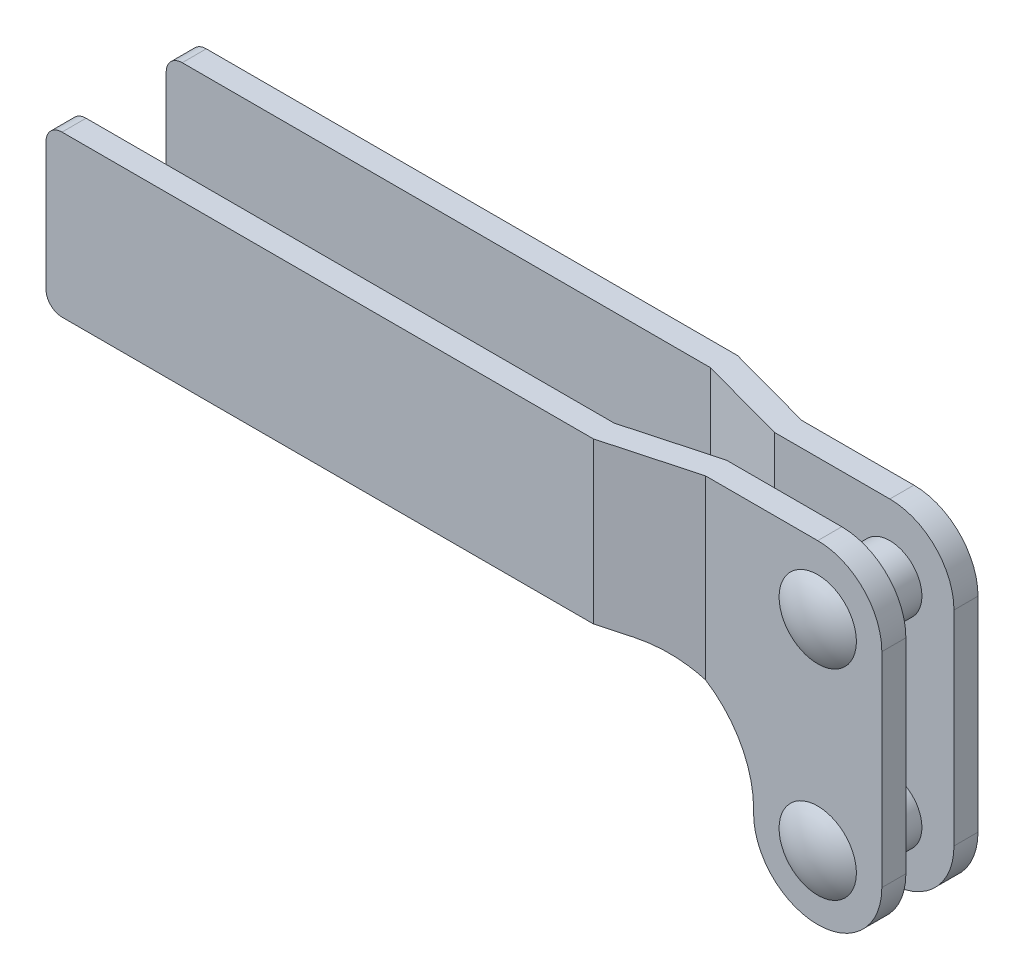
SolidWorks part; units mm, degrees
ref_plane "前视基准面" through (0, 0, 0) normal (0, 0, 1) x (1, 0, 0)
ref_plane "上视基准面" through (0, 0, 0) normal (0, 1, 0) x (1, 0, 0)
ref_plane "右视基准面" through (0, 0, 0) normal (1, 0, 0) x (0, 0, -1)
ref_plane "基准面1" through (0, 0, 0) normal (0, 1, 0) x (1, 0, 0)
ref_plane "基准面2" through (0, -8, 0) normal (0, 1, 0) x (1, 0, 0)
sketch "草图1" plane through (0, -8, 0) normal (0, 1, 0) x (1, 0, 0)
  line L0 (-93.3, -6) -> (-93.3, -9)
  line L1 (-93.3, -9) -> (-25, -9)
  line L2 (-25, -9) -> (-14, -6)
  line L3 (-14, -6) -> (8, -6)
  line L4 (8, -6) -> (8, -3)
  line L5 (8, -3) -> (-14.4018, -3)
  line L6 (-14.4018, -3) -> (-25.4018, -6)
  line L7 (-25.4018, -6) -> (-93.3, -6)
extrude "凸台-拉伸1" add sketch "草图1" along normal blind 41.5
ref_plane "基准面3" through (0, 0, 0) normal (1, 0, 0) x (0, 0, -1)
sketch "草图2" plane through (0, 0, 0) normal (1, 0, 0) x (0, 0, -1)
  line L0 (-6, 4.8218) -> (-6, 4)
  line L1 (-6, 4) -> (6, 4)
  line L2 (6, 4) -> (6, 4.5)
  line L3 (6, 4.5) -> (7, 4.5)
  line L4 (7, 4.5) -> (7, 0)
  line L5 (7, 0) -> (-7.5, 0)
  line L6 (7, 0) -> (-7.5, 0) construction
  arc A0 (-7.5, 0) -> (-6, 4.8218) centre (1, 0) cw
revolve "旋转1" add sketch "草图2" angle 360 about L6 reverse direction yes
sketch "草图3" plane through (0, 0, 0) normal (1, 0, 0) x (0, 0, -1)
  line L0 (-6, 29.8218) -> (-6, 29)
  line L1 (-6, 29) -> (6, 29)
  line L2 (6, 29) -> (6, 29.5)
  line L3 (6, 29.5) -> (7, 29.5)
  line L4 (7, 29.5) -> (7, 25)
  line L5 (7, 25) -> (-7.5, 25)
  line L6 (7, 25) -> (-7.5, 25) construction
  arc A0 (-7.5, 25) -> (-6, 29.8218) centre (1, 25) cw
revolve "旋转2" add sketch "草图3" angle 360 about L6 reverse direction yes
ref_plane "基准面4" through (0, 0, 0) normal (0, 1, 0) x (1, 0, 0)
ref_plane "基准面5" through (0, -8, 0) normal (0, 1, 0) x (1, 0, 0)
sketch "草图4" plane through (0, -8, 0) normal (0, 1, 0) x (1, 0, 0)
  line L0 (-93.3, 6) -> (-25.4018, 6)
  line L1 (-25.4018, 6) -> (-14.4018, 3)
  line L2 (-14.4018, 3) -> (8, 3)
  line L3 (8, 3) -> (8, 6)
  line L4 (8, 6) -> (-14, 6)
  line L5 (-14, 6) -> (-25, 9)
  line L6 (-25, 9) -> (-93.3, 9)
  line L7 (-93.3, 9) -> (-93.3, 6)
extrude "凸台-拉伸2" add sketch "草图4" along normal blind 41.5
ref_plane "基准面6" through (0, 0, 0) normal (0, 0, 1) x (1, 0, 0)
sketch "草图5" plane through (0, 0, 0) normal (0, 0, 1) x (1, 0, 0)
  line L0 (-199.7871, -103.7934) -> (111.8682, -103.7934)
  line L1 (111.8682, -103.7934) -> (111.8682, 145.8801)
  line L2 (111.8682, 145.8801) -> (-199.7871, 145.8801)
  line L3 (-199.7871, 145.8801) -> (-199.7871, -103.7934)
  line L4 (-91.3, 13.5) -> (-21, 13.5)
  line L5 (-8, 0.5) -> (-8, 0)
  line L6 (8, 0) -> (8, 25.5)
  line L7 (0, 33.5) -> (-91.3, 33.5)
  line L8 (-93.3, 31.5) -> (-93.3, 15.5)
  arc A0 (-93.3, 15.5) -> (-91.3, 13.5) centre (-91.3, 15.5) ccw
  arc A1 (-21, 13.5) -> (-8, 0.5) centre (-21, 0.5) cw
  arc A2 (-8, 0) -> (8, 0) centre (0, 0) ccw
  arc A3 (8, 25.5) -> (0, 33.5) centre (0, 25.5) ccw
  arc A4 (-91.3, 33.5) -> (-93.3, 31.5) centre (-91.3, 31.5) ccw
extrude "切除-拉伸1" cut sketch "草图5" along normal blind 9 and the other way blind 9
ref_plane "基准面7" through (-74.2, 0, 0) normal (1, 0, 0) x (0, 0, -1)
ref_plane "基准面8" through (0, -18.5, 0) normal (0, 1, 0) x (1, 0, 0)
ref_plane "cp3 XY" through (0, 0, 0) normal (0, 0, -1) x (-1, 0, 0)
ref_plane "cp3 XZ" through (0, 25, 0) normal (0, 1, 0) x (1, 0, 0)
ref_plane "cp3 YZ" through (0, 0, 0) normal (1, 0, 0) x (0, 0, -1)
ref_axis "cp3 X" through (-80.9, 25, 0) along (1, 0, 0)
ref_axis "cp3 Y" through (0, 50, 0) along (0, -1, 0)
ref_axis "cp3 Z" through (0, 25, -80.9) along (0, 0, 1)
sketch3d "cp3"
  point P0 (0, 25, 0)
ref_plane "cp4 XY" through (0, 0, 0) normal (0, 0, -1) x (-1, 0, 0)
ref_plane "cp4 XZ" through (0, 0, 0) normal (0, 1, 0) x (1, 0, 0)
ref_plane "cp4 YZ" through (0, 0, 0) normal (1, 0, 0) x (0, 0, -1)
ref_axis "cp4 X" through (-80.9, 0, 0) along (1, 0, 0)
ref_axis "cp4 Y" through (0, 50, 0) along (0, -1, 0)
ref_axis "cp4 Z" through (0, 0, -80.9) along (0, 0, 1)
sketch3d "cp4"
  point P0 (0, 0, 0)
ref_plane "to_washer1 XY" through (-74.2, 0, 0) normal (1, 0, 0) x (0, 0, -1)
ref_plane "to_washer1 XZ" through (0, 33.5, 0) normal (0, -1, 0) x (-1, 0, 0)
ref_plane "to_washer1 YZ" through (0, 0, 0) normal (0, 0, -1) x (-1, 0, 0)
ref_axis "to_washer1 X" through (-74.2, 33.5, 80.9) along (0, 0, -1)
ref_axis "to_washer1 Y" through (-74.2, -50, 0) along (0, 1, 0)
ref_axis "to_washer1 Z" through (80.9, 33.5, 0) along (-1, 0, 0)
sketch3d "to_washer1"
  point P0 (-74.2, 33.5, 0)
ref_plane "to_washer2 XY" through (-74.2, 0, 0) normal (1, 0, 0) x (0, 0, -1)
ref_plane "to_washer2 XZ" through (0, 13.5, 0) normal (0, -1, 0) x (-1, 0, 0)
ref_plane "to_washer2 YZ" through (0, 0, 0) normal (0, 0, -1) x (-1, 0, 0)
ref_axis "to_washer2 X" through (-74.2, 13.5, 80.9) along (0, 0, -1)
ref_axis "to_washer2 Y" through (-74.2, -50, 0) along (0, 1, 0)
ref_axis "to_washer2 Z" through (80.9, 13.5, 0) along (-1, 0, 0)
sketch3d "to_washer2"
  point P0 (-74.2, 13.5, 0)
ref_plane "to_bolt XY" through (0, -18.5, 0) normal (0, -1, 0) x (-1, 0, 0)
ref_plane "to_bolt XZ" through (0, 0, 0) normal (0, 0, -1) x (-1, 0, 0)
ref_plane "to_bolt YZ" through (-74.25, 0, 0) normal (1, 0, 0) x (0, 0, -1)
ref_axis "to_bolt X" through (-80.9, -18.5, 0) along (1, 0, 0)
ref_axis "to_bolt Y" through (-74.25, -18.5, -50) along (0, 0, 1)
ref_axis "to_bolt Z" through (-74.25, -50, 0) along (0, 1, 0)
sketch3d "to_bolt"
  point P0 (-74.25, -18.5, 0)
equation "\"零件重量\"= \"SW-质量\""
